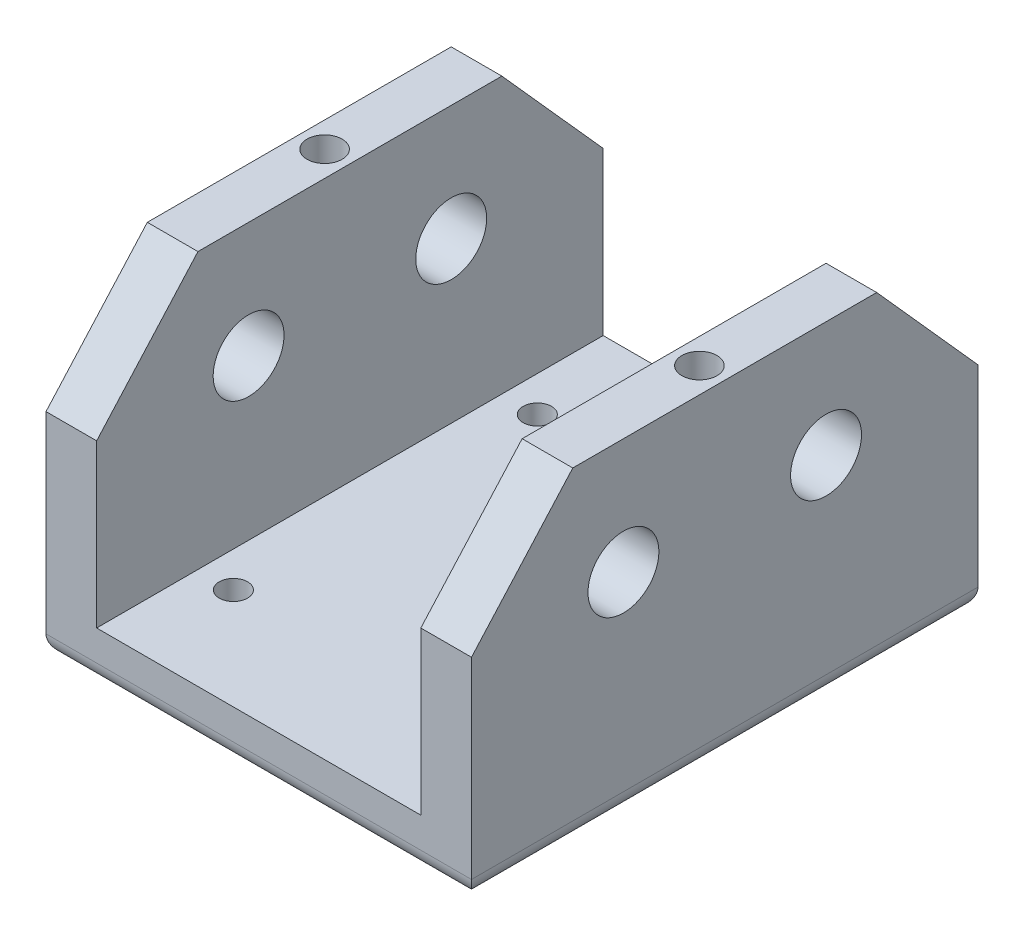
SolidWorks part; units mm, degrees
ref_plane "Front Plane" through (0, 0, 0) normal (0, 0, 1) x (1, 0, 0)
ref_plane "Top Plane" through (0, 0, 0) normal (0, 1, 0) x (1, 0, 0)
ref_plane "Right Plane" through (0, 0, 0) normal (1, 0, 0) x (0, 0, -1)
ref_plane "MiddlePlane" through (-26.67, 0, 0) normal (1, 0, 0) x (0, 0, -1)
sketch "Sketch1" plane through (0, 0, 0) normal (1, 0, 0) x (0, 0, -1)
  line L1 (0, 0) -> (63.5, 0)
  line L2 (0, 0) -> (0, 6.35)
  line L3 (0, 6.35) -> (63.5, 6.35)
  line L4 (63.5, 0) -> (63.5, 6.35)
  dimension "D1" = 6.35
  dimension "D2" = 63.5
extrude "Boss-Extrude1" add sketch "Sketch1" against normal blind 53.34
sketch "Sketch2" plane through (0, 0, 0) normal (1, 0, 0) x (0, 0, -1)
  line L0 (0, 6.35) -> (0, 26.67)
  line L1 (0, 26.67) -> (12.7, 40.869)
  line L2 (12.7, 40.869) -> (50.8, 40.869)
  line L3 (50.8, 40.869) -> (63.5, 26.67)
  line L4 (63.5, 26.67) -> (63.5, 6.35)
  line L5 (63.5, 6.35) -> (0, 6.35)
  point P7 (31.75, 40.869)
  point P10 (31.75, 6.35)
  dimension "D1" = 38.1
  dimension "D2" = 20.32
  dimension "D4" = 19.05
  dimension "D5" = 19.05
extrude "Boss-Extrude2" add sketch "Sketch2" against normal blind 6.35
sketch "Sketch11" plane through (0, 0, 0) normal (1, 0, 0) x (0, 0, -1)
  line L3 (50.8, 40.869) -> (12.7, 40.869) construction
  line L4 (0, 26.67) -> (0, 0) construction
  line L5 (63.5, 0) -> (63.5, 26.67) construction
  circle A4 centre (19.05, 26.391) radius 4.445
  circle A5 centre (44.45, 26.391) radius 4.445
  dimension "D1" = 8.89
  dimension "D3" = 19.05
  dimension "D4" = 19.05
  dimension "D2" = 14.478
extrude "Cut-Extrude1" cut sketch "Sketch11" against normal up to next
ref_plane "Plane2" through (0, 33.02, 0) normal (0, -1, 0) x (-1, 0, 0)
fillet "Fillet1" radius 2.54 4 edges at (0, 0, -31.75) (-26.67, 0, -63.5) (-53.34, 0, -31.75) (-26.67, 0, 0)
sketch "Sketch19" plane through (0, 0, 0) normal (0, -1, 0) x (1, 0, 0)
  line L0 (-26.67, -63.5) -> (-26.67, 0) construction
  line L1 (0, -63.5) -> (-53.34, -63.5) construction
  line L2 (-53.34, 0) -> (0, 0) construction
  line L3 (0, -31.75) -> (-53.34, -31.75) construction
  line L4 (0, 0) -> (0, -63.5) construction
  line L5 (-53.34, -63.5) -> (-53.34, 0) construction
  line L7 (-10.795, -50.8) -> (-42.545, -50.8) construction
  line L8 (-10.795, -50.8) -> (-10.795, -12.7) construction
  line L9 (-10.795, -12.7) -> (-42.545, -12.7) construction
  line L10 (-42.545, -50.8) -> (-42.545, -12.7) construction
  line L11 (-10.795, -50.8) -> (-42.545, -12.7) construction
  line L12 (-10.795, -12.7) -> (-42.545, -50.8) construction
  circle A0 centre (-10.795, -50.8) radius 1.778
  circle A1 centre (-42.545, -50.8) radius 1.778
  circle A2 centre (-42.545, -12.7) radius 1.778
  circle A3 centre (-10.795, -12.7) radius 1.778
  point P12 (-26.67, -31.75)
  dimension "D3" = 3.556
  dimension "D1" = 31.75
  dimension "D2" = 38.1
extrude "Cut-Extrude2" cut sketch "Sketch19" against normal up to next
mirror "Mirror1" about plane through (-26.67, 0, 0) normal (1, 0, 0) of "Cut-Extrude1", "Boss-Extrude2"
sketch "Sketch20" plane through (0, 40.869, 0) normal (0, 1, 0) x (1, 0, 0)
  line L0 (0, 31.75) -> (-53.34, 31.75) construction
  line L1 (0, 50.8) -> (0, 12.7) construction
  line L2 (-53.34, 50.8) -> (-53.34, 12.7) construction
  line L4 (-50.165, 50.8) -> (-50.165, 12.7) construction
  line L5 (-46.99, 50.8) -> (-53.34, 50.8) construction
  line L6 (-46.99, 12.7) -> (-53.34, 12.7) construction
  line L7 (-26.67, 63.5) -> (-26.67, 0) construction
  line L8 (-46.99, 63.5) -> (-6.35, 63.5) construction
  line L9 (-46.99, 0) -> (-6.35, 0) construction
  circle A4 centre (-50.165, 31.75) radius 2.2
  circle A5 centre (-3.175, 31.75) radius 2.2
  point P9 (-50.165, 31.75)
  dimension "D1" = 4.4
extrude "Cut-Extrude3" cut sketch "Sketch20" against normal blind 4.9
